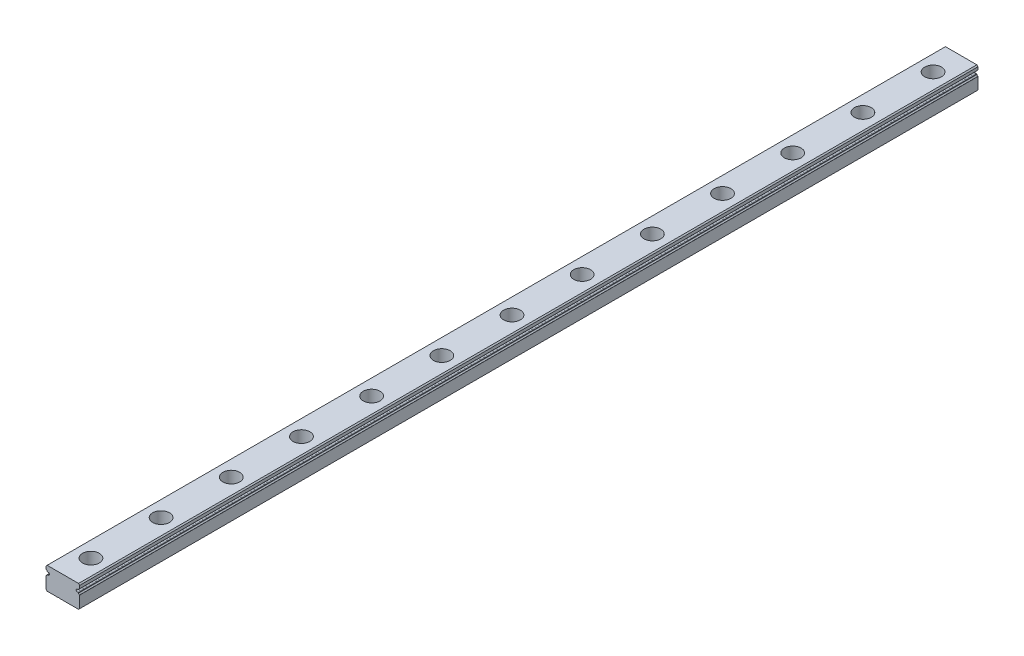
SolidWorks part; units mm, degrees
material "Acero al carbono no aleado"
ref_plane "Alzado" through (0, 0, 0) normal (0, 0, 1) x (1, 0, 0)
ref_plane "Planta" through (0, 0, 0) normal (0, 1, 0) x (1, 0, 0)
ref_plane "Vista lateral" through (0, 0, 0) normal (1, 0, 0) x (0, 0, -1)
ref_plane "Plano1" through (0, 4.0507, 0) normal (0, 1, 0) x (1, 0, 0)
sketch "Croquis1" plane through (0, 4.0507, 0) normal (0, 1, 0) x (1, 0, 0)
  line L0 (6, 250) -> (-6, 250)
  line L1 (-6, 250) -> (-6, -250)
  line L2 (-6, -250) -> (6, -250)
  line L3 (6, -250) -> (6, 250)
extrude "Saliente-Extruir1" add sketch "Croquis1" against normal blind 8
sketch "Croquis2" plane through (0, 0, -250) normal (0, 0, -1) x (-1, 0, 0)
  line L0 (1.35, -3.9493) -> (1.85, -3.9493)
  arc A0 (1.85, -3.9493) -> (1.35, -3.9493) centre (1.6, -4.2118) ccw
extrude "Cortar-Extruir1" cut sketch "Croquis2" against normal through all
sketch "Croquis3" plane through (0, 0, -250) normal (0, 0, -1) x (-1, 0, 0)
  line L0 (-6, 2.1007) -> (-6, 1.2007)
  line L1 (-6, 1.2007) -> (-5.2, 1.2007)
  line L2 (-5.2, 2.1007) -> (-6, 2.1007)
  arc A0 (-5.2, 1.2007) -> (-5.2, 2.1007) centre (-5.2, 1.6507) ccw
extrude "Cortar-Extruir2" cut sketch "Croquis3" against normal through all
sketch "Croquis4" plane through (0, 0, -250) normal (0, 0, -1) x (-1, 0, 0)
  line L0 (-5.6226, 1.2007) -> (-6, 1.2007)
  line L1 (-6, 1.2007) -> (-6, 0.6893)
  arc A0 (-6, 0.6893) -> (-5.6226, 1.2007) centre (-6.0067, 1.0892) ccw
extrude "Cortar-Extruir3" cut sketch "Croquis4" against normal through all
sketch "Croquis5" plane through (0, 0, -250) normal (0, 0, -1) x (-1, 0, 0)
  line L0 (-6, 2.612) -> (-6, 2.1007)
  line L1 (-6, 2.1007) -> (-5.6226, 2.1007)
  arc A0 (-5.6226, 2.1007) -> (-6, 2.612) centre (-6.0067, 2.2121) ccw
extrude "Cortar-Extruir4" cut sketch "Croquis5" against normal through all
sketch "Croquis6" plane through (0, 0, -250) normal (0, 0, -1) x (-1, 0, 0)
  line L0 (6, 1.2007) -> (6, 2.1007)
  line L1 (6, 2.1007) -> (5.2, 2.1007)
  line L2 (5.2, 1.2007) -> (6, 1.2007)
  arc A0 (5.2, 2.1007) -> (5.2, 1.2007) centre (5.2, 1.6507) ccw
extrude "Cortar-Extruir5" cut sketch "Croquis6" against normal through all
sketch "Croquis7" plane through (0, 0, -250) normal (0, 0, -1) x (-1, 0, 0)
  line L0 (5.6226, 2.1007) -> (6, 2.1007)
  line L1 (6, 2.1007) -> (6, 2.612)
  arc A0 (6, 2.612) -> (5.6226, 2.1007) centre (6.0067, 2.2121) ccw
extrude "Cortar-Extruir6" cut sketch "Croquis7" against normal through all
sketch "Croquis8" plane through (0, 0, -250) normal (0, 0, -1) x (-1, 0, 0)
  line L0 (6, 0.6893) -> (6, 1.2007)
  line L1 (6, 1.2007) -> (5.6226, 1.2007)
  arc A0 (5.6226, 1.2007) -> (6, 0.6893) centre (6.0067, 1.0892) ccw
extrude "Cortar-Extruir7" cut sketch "Croquis8" against normal through all
hole_wizard "Refrentado para tornillo con cabeza hexagonal de M31" positions "Croquis10" profile "Croquis9" counterbore size "M3" standard "Ansi Metric"
sketch "Croquis10" plane through (0, 4.0507, 0) normal (0, 1, 0) x (1, 0, 0)
  point P0 (0, -240)
  point P1 (0, -215)
  point P2 (0, -190)
  point P3 (0, -165)
  point P4 (0, -140)
  point P5 (0, -115)
  point P6 (0, -90)
  point P7 (0, -65)
  point P8 (0, -40)
  point P9 (0, -15)
  point P10 (0, 10)
  point P11 (0, 35)
  point P12 (0, 60)
  point P13 (0, 85)
  point P14 (0, 110)
  point P15 (0, 135)
  point P16 (0, 160)
  point P17 (0, 185)
  point P18 (0, 210)
  point P19 (0, 235)
sketch "Croquis9" plane through (0, 4.0507, 240) normal (1, 0, 0) x (0, 0, 1)
  line L0 (0, 0) -> (0, 8)
  line L1 (0, 8) -> (1.75, 8)
  line L3 (1.75, 8) -> (1.75, 4.5)
  line L4 (1.75, 4.5) -> (3, 4.5)
  line L5 (3, 4.5) -> (3, 0)
  line L7 (3, 0) -> (0, 0)
  line L11 (0, -6.35) -> (0, 107.95) construction
  dimension "Diámetro de taladro hasta el siguiente" = 3.5
  dimension "Profundidad de taladro hasta el siguiente" = 8
  dimension "Diámetro de refrentado" = 6
  dimension "Profundidad de refrentado" = 4.5
chamfer "Chaflán1" distance 0.4 angle 45 4 edges at (-6, -3.9493, 0) (-6, 4.0507, 0) (6, -3.9493, 0) (6, 4.0507, 0)
chamfer "Chaflán2" distance 0.0369 angle 42.274 4 edges at (-6, 2.612, 0) (6, 0.6893, 0) (-6, 0.6893, 0) (6, 2.612, 0) first distance on face at (-5.7481, 2.403, 0) first distance on face at (5.7481, 0.8983, 0) first distance on face at (-6, -1.43, 0) first distance on face at (6, 3.1313, 0)
chamfer "Chaflán3" distance 0.105 angle 47.726 4 edges at (-5.6226, 1.2007, 0) (5.6226, 1.2007, 0) (-5.6226, 2.1007, 0) (5.6226, 2.1007, 0) first distance on face at (-5.4113, 1.2007, 0) first distance on face at (5.7328, 0.907, 0) first distance on face at (-5.7328, 2.3943, 0) first distance on face at (5.4113, 2.1007, 0)
sketch "Croquis11" plane through (0, 0, -250) normal (0, 0, -1) x (-1, 0, 0)
  line L1 (9.7177, -7.8005) -> (-11.676, -7.8005)
  line L2 (9.7177, -7.8005) -> (9.7177, 11.7122)
  line L3 (9.7177, 11.7122) -> (-11.676, 11.7122)
  line L4 (-11.676, -7.8005) -> (-11.676, 11.7122)
extrude "Cortar-Extruir8" cut sketch "Croquis11" against normal blind 180
